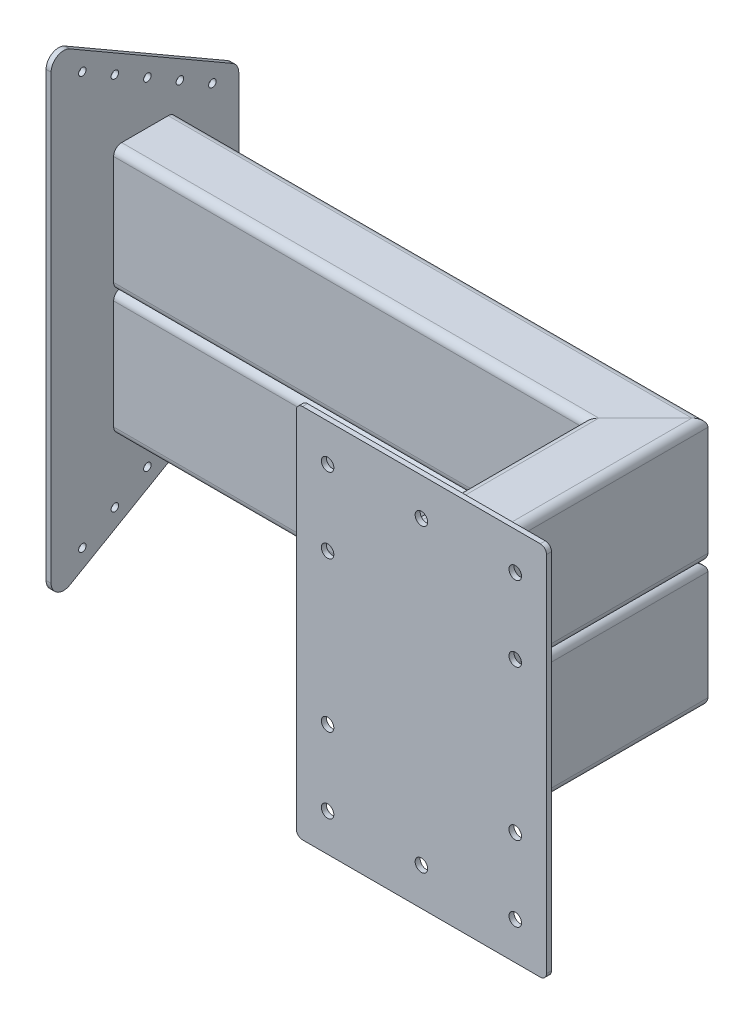
SolidWorks part; units mm, degrees
ref_plane "Front Plane" through (0, 0, 0) normal (0, 0, 1) x (1, 0, 0)
ref_plane "Top Plane" through (0, 0, 0) normal (0, 1, 0) x (1, 0, 0)
ref_plane "Right Plane" through (0, 0, 0) normal (1, 0, 0) x (0, 0, -1)
sketch "Sketch1" plane through (0, 0, 0) normal (0, 1, 0) x (1, 0, 0)
  line L0 (0, 0) -> (400, 0)
  line L1 (400, 0) -> (400, -175)
  dimension "D1" = 400
  dimension "D2" = 90
  dimension "D3" = 175
other "Tube (rectangular) 100 X 50 X 3.2(3)" corner treatment miter
ref_plane "Plane1" through (0, 0, 0) normal (1, 0, 0) x (0, 0, -1)
sketch "Sketch11" plane through (0, 0, 0) normal (1, 0, 0) x (0, 0, -1)
  line L0 (-18.6, -46.8) -> (18.6, -46.8)
  line L1 (-21.8, -43.6) -> (-21.8, 43.6)
  line L2 (18.6, 46.8) -> (-18.6, 46.8)
  line L3 (21.8, 43.6) -> (21.8, -43.6)
  line L4 (-18.6, -50) -> (18.6, -50)
  line L5 (-25, -43.6) -> (-25, 43.6)
  line L6 (18.6, 50) -> (-18.6, 50)
  line L7 (25, 43.6) -> (25, -43.6)
  line L8 (-25, 0) -> (-21.8, 0) construction
  line L9 (-21.8, 0) -> (21.8, 0) construction
  line L10 (21.8, 0) -> (25, 0) construction
  line L11 (0, 50) -> (0, 46.8) construction
  line L12 (0, 46.8) -> (0, -46.8) construction
  line L13 (0, -46.8) -> (0, -50) construction
  arc A0 (25, 43.6) -> (18.6, 50) centre (18.6, 43.6) ccw
  arc A1 (18.6, -50) -> (25, -43.6) centre (18.6, -43.6) ccw
  arc A2 (-25, -43.6) -> (-18.6, -50) centre (-18.6, -43.6) ccw
  arc A3 (-18.6, 50) -> (-25, 43.6) centre (-18.6, 43.6) ccw
  arc A4 (-18.6, 46.8) -> (-21.8, 43.6) centre (-18.6, 43.6) ccw
  arc A5 (21.8, 43.6) -> (18.6, 46.8) centre (18.6, 43.6) ccw
  arc A6 (18.6, -46.8) -> (21.8, -43.6) centre (18.6, -43.6) ccw
  arc A7 (-21.8, -43.6) -> (-18.6, -46.8) centre (-18.6, -43.6) ccw
  point P6 (-25, 50)
  point P33 (-25, -50)
  point P34 (25, -50)
  point P36 (25, 50)
  point P37 (0, 0)
  dimension "D1" = 6.4
  dimension "Thickness" = 3.2
  dimension "V_leg" = 100
  dimension "H_leg" = 50
ref_plane "Plane2" through (0, 100, 0) normal (0, 1, 0) x (1, 0, 0)
sketch "Sketch12" plane through (0, 100, 0) normal (0, 1, 0) x (1, 0, 0)
  line L0 (400, 0) -> (400, -175) construction
  line L1 (0, 0) -> (400, 0) construction
  line L2 (400, 0) -> (400, -175)
  line L3 (0, 0) -> (400, 0)
other "Tube (rectangular) 100 X 50 X 3.2(4)" corner treatment miter
ref_plane "Plane4" through (0, 100, 0) normal (1, 0, 0) x (0, 0, -1)
sketch "Sketch14" plane through (0, 100, 0) normal (1, 0, 0) x (0, 0, -1)
  line L0 (-18.6, -46.8) -> (18.6, -46.8)
  line L1 (-21.8, -43.6) -> (-21.8, 43.6)
  line L2 (18.6, 46.8) -> (-18.6, 46.8)
  line L3 (21.8, 43.6) -> (21.8, -43.6)
  line L4 (-18.6, -50) -> (18.6, -50)
  line L5 (-25, -43.6) -> (-25, 43.6)
  line L6 (18.6, 50) -> (-18.6, 50)
  line L7 (25, 43.6) -> (25, -43.6)
  line L8 (-25, 0) -> (-21.8, 0) construction
  line L9 (-21.8, 0) -> (21.8, 0) construction
  line L10 (21.8, 0) -> (25, 0) construction
  line L11 (0, 50) -> (0, 46.8) construction
  line L12 (0, 46.8) -> (0, -46.8) construction
  line L13 (0, -46.8) -> (0, -50) construction
  arc A0 (25, 43.6) -> (18.6, 50) centre (18.6, 43.6) ccw
  arc A1 (18.6, -50) -> (25, -43.6) centre (18.6, -43.6) ccw
  arc A2 (-25, -43.6) -> (-18.6, -50) centre (-18.6, -43.6) ccw
  arc A3 (-18.6, 50) -> (-25, 43.6) centre (-18.6, 43.6) ccw
  arc A4 (-18.6, 46.8) -> (-21.8, 43.6) centre (-18.6, 43.6) ccw
  arc A5 (21.8, 43.6) -> (18.6, 46.8) centre (18.6, 43.6) ccw
  arc A6 (18.6, -46.8) -> (21.8, -43.6) centre (18.6, -43.6) ccw
  arc A7 (-21.8, -43.6) -> (-18.6, -46.8) centre (-18.6, -43.6) ccw
  point P6 (-25, 50)
  point P33 (-25, -50)
  point P34 (25, -50)
  point P36 (25, 50)
  point P37 (0, 0)
  dimension "D1" = 6.4
  dimension "Thickness" = 3.2
  dimension "V_leg" = 100
  dimension "H_leg" = 50
sketch "Sketch18" plane through (0, -50, 0) normal (0, -1, 0) x (1, 0, 0)
  line L0 (0, 18.6) -> (0, -18.6) construction
  line L1 (300, 175) -> (500, 175)
  line L2 (300, 175) -> (300, 179)
  line L3 (300, 179) -> (500, 179)
  line L4 (500, 175) -> (500, 179)
  line L5 (300, 175) -> (500, 179) construction
  line L6 (300, 179) -> (500, 175) construction
  line L7 (0, 75) -> (-4, 75)
  line L8 (0, 75) -> (0, -75)
  line L9 (0, -75) -> (-4, -75)
  line L10 (-4, 75) -> (-4, -75)
  line L11 (0, 75) -> (-4, -75) construction
  line L12 (0, -75) -> (-4, 75) construction
  line L13 (375, 25) -> (0, 25) construction
  point P0 (400, 177)
  point P7 (-2, 0)
  dimension "D1" = 200
  dimension "D2" = 4
  dimension "D3" = 0
  dimension "D4" = 0
  dimension "D5" = 4
  dimension "D6" = 150
  dimension "D7" = 0
  dimension "D8" = 0
  dimension "D9" = 50
extrude "Boss-Extrude1" add sketch "Sketch18" against normal blind 300 and the other way blind 100 separate body
other "Trim/Extend1"
chamfer "Chamfer1" distance 160 angle 30 1 edges at (-2, 250, -75) first distance on face at (-2, 250, 0)
chamfer "Chamfer2" distance 160 angle 30 1 edges at (-2, -150, -75) first distance on face at (-2, -150, 0)
sketch "Sketch20" [suppressed] plane through (-4, 0, 0) normal (-1, 0, 0) x (0, 0, 1)
  line L0 (-75, -36.4915) -> (-75, 136.4915) construction
  line L1 (75, -60) -> (75, 200) construction
  circle A0 centre (-50, 109.5085) radius 5
  circle A1 centre (-50, 49.5085) radius 5
  circle A2 centre (-50, -10.4915) radius 5
  circle A3 centre (50, 140) radius 5
  circle A4 centre (50, 80) radius 5
  circle A5 centre (50, 20) radius 5
  circle A6 centre (50, -40) radius 5
  dimension "D1" = 10
  dimension "D2" = 10
  dimension "D3" = 10
  dimension "D4" = 10
  dimension "D5" = 10
  dimension "D6" = 10
  dimension "D7" = 10
  dimension "D8" = 25
  dimension "D9" = 25
  dimension "D10" = 25
  dimension "D11" = 25
  dimension "D12" = 25
  dimension "D13" = 25
  dimension "D14" = 25
  dimension "D15" = 60
  dimension "D16" = 60
  dimension "D17" = 60
  dimension "D18" = 60
  dimension "D19" = 60
  dimension "D20" = 26
  dimension "D21" = 60
extrude "Cut-Extrude1" [suppressed] cut sketch "Sketch20" against normal up to next
sketch "Sketch21" plane through (0, 0, 179) normal (0, 0, 1) x (1, 0, 0)
  line L0 (300, -150) -> (300, 250) construction
  line L1 (500, 250) -> (300, 250) construction
  line L2 (299.6, -223.0536) -> (299.6, 323.0536) construction
  line L3 (500, 250) -> (299.6, 250)
  line L4 (500, 250) -> (500, 200)
  line L5 (500, 200) -> (299.6, 200)
  line L6 (299.6, 250) -> (299.6, 200)
  line L7 (500, -150) -> (500, 250) construction
  line L8 (300, -150) -> (500, -150)
  line L9 (300, -150) -> (300, -100)
  line L10 (300, -100) -> (500, -100)
  line L11 (500, -150) -> (500, -100)
  circle A0 centre (325, 170) radius 5
  circle A1 centre (400, 170) radius 5
  circle A2 centre (475, 170) radius 5
  circle A3 centre (400, -70) radius 5
  circle A4 centre (475, -70) radius 5
  circle A5 centre (325, -70) radius 5
  circle A6 centre (325, 110) radius 5
  circle A7 centre (475, 110) radius 5
  circle A10 centre (325, -10) radius 5
  circle A11 centre (475, -10) radius 5
  circle A12 centre (475, 50) radius 5 [skipped]
  circle A13 centre (325, 50) radius 5 [skipped]
  dimension "D1" = 10
  dimension "D2" = 25
  dimension "D3" = 80
  dimension "D7" = 50
  dimension "D8" = 50
  dimension "D4" = 3
  dimension "D5" = 2
  dimension "D6" = 4
extrude "Cut-Extrude2" cut sketch "Sketch21" against normal up to next (4 mm away)
fillet "Fillet6" radius 5 4 edges at (300, -100, 177) (500, -100, 177) (300, 200, 177) (500, 200, 177)
fillet "Fillet8" radius 10 4 edges at (-2, -144.2265, 75) (-2, -57.624, -75) (-2, 244.2265, 75) (-2, 157.624, -75)
sketch "Sketch22" plane through (0, 0, 0) normal (1, 0, 0) x (0, 0, -1)
  line L0 (-60, -135.5662) -> (70, -60.5107) construction
  line L1 (-75, -126.906) -> (-75, 226.906) construction
  line L3 (70, 160.5107) -> (-60, 235.5662) construction
  circle A0 centre (-50, -114.7816) radius 3
  circle A1 centre (-24.0192, -99.7816) radius 3
  circle A2 centre (1.9615, -84.7816) radius 3
  circle A3 centre (27.9423, -69.7816) radius 3
  circle A4 centre (53.923, -54.7816) radius 3
  circle A5 centre (-50, 214.7816) radius 3
  circle A6 centre (-24.0192, 199.7816) radius 3
  circle A7 centre (1.9615, 184.7816) radius 3
  circle A8 centre (27.9423, 169.7816) radius 3
  circle A9 centre (53.923, 154.7816) radius 3
  dimension "D1" = 6
  dimension "D2" = 6
  dimension "D3" = 6
  dimension "D4" = 6
  dimension "D5" = 6
  dimension "D16" = 6
  dimension "D17" = 6
  dimension "D18" = 6
  dimension "D19" = 6
  dimension "D20" = 6
  dimension "D6" = 13
  dimension "D7" = 13
  dimension "D8" = 13
  dimension "D9" = 13
  dimension "D10" = 13
  dimension "D11" = 30
  dimension "D12" = 30
  dimension "D13" = 30
  dimension "D14" = 30
  dimension "D15" = 25
  dimension "D21" = 13
  dimension "D22" = 13
  dimension "D23" = 13
  dimension "D24" = 13
  dimension "D25" = 13
  dimension "D26" = 30
  dimension "D27" = 30
  dimension "D28" = 30
  dimension "D29" = 30
  dimension "D30" = 25
extrude "Cut-Extrude3" cut sketch "Sketch22" against normal up to next (4 mm away)
